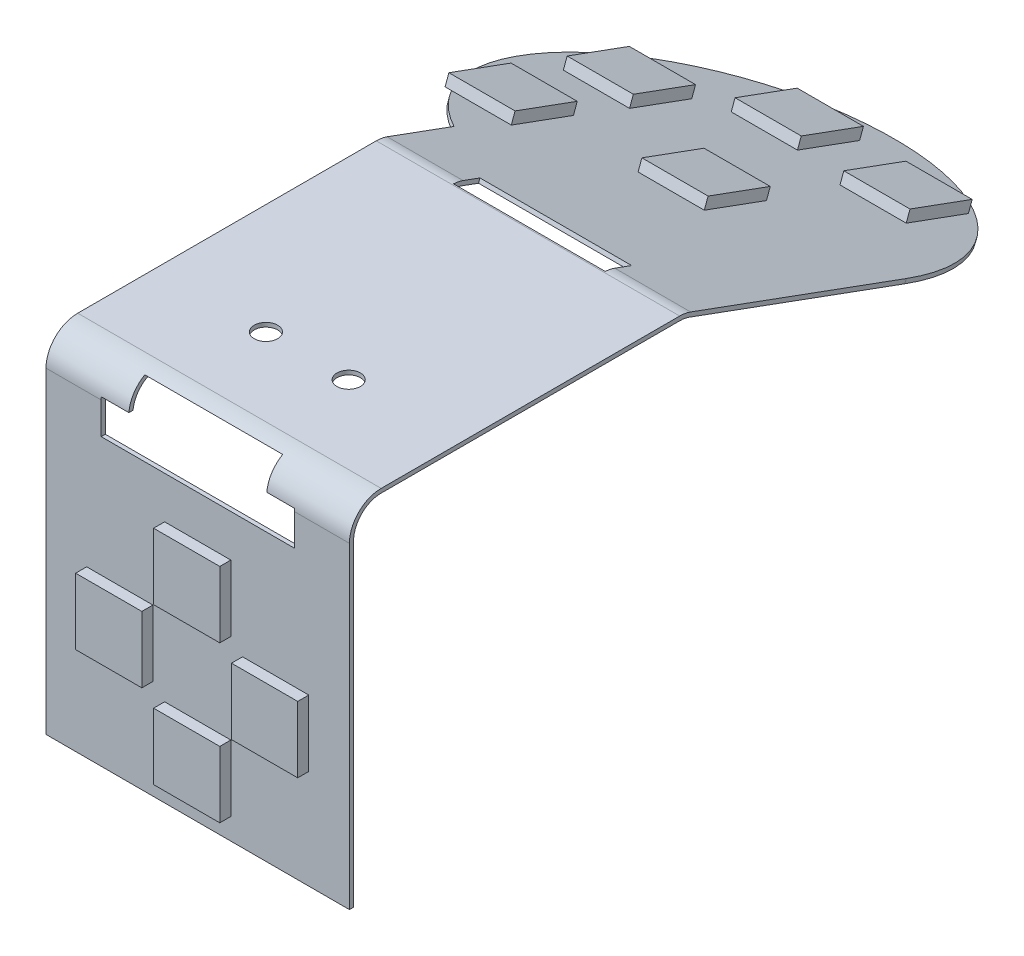
SolidWorks part; units mm, degrees
ref_plane "前视基准面" through (0, 0, 0) normal (0, 0, 1) x (1, 0, 0)
ref_plane "上视基准面" through (0, 0, 0) normal (0, 1, 0) x (1, 0, 0)
ref_plane "右视基准面" through (0, 0, 0) normal (1, 0, 0) x (0, 0, -1)
other "Configuration Table"
sketch "草图1" plane through (0, 0, 0) normal (1, 0, 0) x (0, 0, -1)
  line L0 (0, -25) -> (0, -2)
  line L1 (2, 0) -> (23.6457, 0)
  line L2 (24.3327, -0.1217) -> (52.1746, -10.3049)
  line L3 (-0.3, -25) -> (-0.3, -2)
  line L4 (2, 0.3) -> (23.6457, 0.3)
  line L5 (24.4358, 0.1601) -> (52.2777, -10.0231)
  line L6 (0, -25) -> (-0.3, -25)
  line L7 (52.2777, -10.0231) -> (52.1746, -10.3049)
  arc A0 (23.6457, 0) -> (24.3327, -0.1217) centre (23.6457, -2) cw
  arc A1 (0, -2) -> (2, 0) centre (2, -2) cw
  arc A2 (-0.3, -2) -> (2, 0.3) centre (2, -2) cw
  arc A3 (23.6457, 0.3) -> (24.4358, 0.1601) centre (23.6457, -2) cw
  point P7 (24, 0)
  point P10 (0, 0)
  dimension "D5" = 2
  dimension "D1" = 25
  dimension "D2" = 24
  dimension "D3" = 159.91
  dimension "D4" = 30
  dimension "D6" = 0.3
extrude "凸台-拉伸1" add sketch "草图1" along normal blind 22
sketch "草图2" plane through (0, 0, 0.3) normal (0, 0, 1) x (1, 0, 0)
  line L0 (22, 0.3) -> (0, 0.3) construction
  line L1 (4, -4.3) -> (18, -4.3)
  line L2 (4, -4.3) -> (4, -1.8)
  line L3 (4, -1.8) -> (18, -1.8)
  line L4 (18, -4.3) -> (18, -1.8)
  line L5 (6, -1.8) -> (16, -1.8)
  line L6 (6, -1.8) -> (6, 0)
  line L7 (6, 0) -> (16, 0)
  line L8 (16, -1.8) -> (16, 0)
  line L10 (11, -26.5654) -> (11, 3.7124) construction
  line L12 (0, -2) -> (0, -25) construction
  line L13 (22, -2) -> (22, -25) construction
  line M13 (22, -2) -> (0, -2)
  dimension "D1" = 1.8
  dimension "D2" = 2.5
  dimension "D3" = 0.3
  dimension "D4" = 14
  dimension "D5" = 10
extrude "切除-拉伸1" cut sketch "草图2" against normal blind 4 contours L3 L10 L7 L6 | L10 L5 L8 L7 | L1 L10 L2 M13 | L10 L1 L4 M13 | L10 L3 L2 M13 | L10 L4 L3 L5 M13 region at (7.5, -3.15, 0.3) region at (14.5, -3.15, 0.3) region at (7.5, -1.9, 0.3) region at (14.5, -1.9, 0.3) region at (13.5, -0.9, 0.3) region at (8.5, -0.9, 0.3)
sketch "草图3" plane through (0, 8.024, -2.9348) normal (0, 0.9392, -0.3435) x (1, 0, 0)
  line L0 (22, 52.5397) -> (22, 22.894) construction
  line L1 (22, 52.5397) -> (0, 52.5397) construction
  circle A0 centre (8, 39.5397) radius 14
  point P2 (6.1666, 43.208)
  point P5 (9.278, 41.7079)
  point P6 (7.5557, 40.2633)
  point P7 (0, 0)
  point P8 (7.5557, 39.8188)
  line M2 (0, 52.5397) -> (0, 22.894)
  line M4 (22, 22.894) -> (22, 52.5397)
  line M5 (22, 52.5397) -> (0, 52.5397)
  dimension "D1" = 28
  dimension "D2" = 13
extrude "切除-拉伸2" cut sketch "草图3" against normal through all contours A0 M4 M5 | A0 M5 M2 region at (19.6053, -8.9881, -49.4478) region at (0.8895, -9.8577, -51.8254)
extrude "凸台-拉伸2" add sketch "草图3<3>" against normal blind 0.3
sketch "草图3<3>" plane through (0, 8.024, -2.9348) normal (0, 0.9392, -0.3435) x (1, 0, 0) same geometry as "草图3"
sketch "草图4" plane through (0, 0, 0.3) normal (0, 0, 1) x (1, 0, 0)
  line L0 (-5.9466, -15.4) -> (23.7502, -15.4) construction
  line L1 (8.6, -7.35) -> (13.4, -7.35)
  line L2 (8.6, -7.35) -> (8.6, -12.15)
  line L3 (8.6, -12.15) -> (13.4, -12.15)
  line L4 (13.4, -7.35) -> (13.4, -12.15)
  line L5 (11, -28.2671) -> (11, 2.5503) construction
  line L6 (0, -2) -> (0, -25) construction
  line L7 (22, -2) -> (22, -25) construction
  line L8 (22, -25) -> (0, -25) construction
  line L9 (8.6, -18.65) -> (13.4, -18.65)
  line L10 (8.6, -18.65) -> (8.6, -23.45)
  line L11 (8.6, -23.45) -> (13.4, -23.45)
  line L12 (13.4, -18.65) -> (13.4, -23.45)
  line L14 (2.95, -13) -> (7.75, -13)
  line L15 (2.95, -13) -> (2.95, -17.8)
  line L16 (2.95, -17.8) -> (7.75, -17.8)
  line L17 (7.75, -13) -> (7.75, -17.8)
  line L18 (14.25, -13) -> (19.05, -13)
  line L19 (14.25, -13) -> (14.25, -17.8)
  line L20 (14.25, -17.8) -> (19.05, -17.8)
  line L21 (19.05, -13) -> (19.05, -17.8)
  dimension "D1" = 4.8
  dimension "D2" = 9.6
  dimension "D3" = 6.5
  dimension "D4" = 6.5
extrude "凸台-拉伸3" add sketch "草图4" along normal blind 0.8
sketch "草图5" plane through (0, 0.3, 0) normal (0, 1, 0) x (1, 0, 0)
  line L0 (11, -6.2283) -> (11, 16.6274) construction
  line L3 (0, 23.6457) -> (0, 2) construction
  line L4 (22, 23.6457) -> (22, 2) construction
  line L5 (22, 23.6457) -> (0, 23.6457) construction
  circle A0 centre (8, 7.6457) radius 0.85
  circle A1 centre (14, 7.6457) radius 0.85
  point P12 (14.286, 6.5162)
  point P13 (14.0837, 6.7475)
  point P14 (13.9604, 6.7191)
  point P15 (13.9984, 6.7286)
  point P18 (0, 0)
  point P20 (12.1537, 6.6694)
  dimension "D1" = 1.7
  dimension "D2" = 16
  dimension "D3" = 3
extrude "切除-拉伸3" cut sketch "草图5" against normal through all
sketch "草图6" plane through (0, 8.024, -2.9348) normal (0, 0.9392, -0.3435) x (1, 0, 0)
  line L0 (11, 16.3664) -> (11, 30.7303) construction
  line L1 (5.5, 22.2) -> (16.5, 22.2)
  line L2 (5.5, 22.2) -> (5.5, 24.2)
  line L3 (5.5, 24.2) -> (16.5, 24.2)
  line L4 (16.5, 22.2) -> (16.5, 24.2)
  line L7 (0, 22.1039) -> (0, 1.7753) construction
  line L8 (22, 22.1039) -> (22, 1.7753) construction
  dimension "D1" = 11
  dimension "D2" = 2
  dimension "D3" = 22.2
extrude "切除-拉伸4" cut sketch "草图6" against normal blind 1
sketch "草图7" plane through (0, 8.024, -2.9348) normal (0, 0.9392, -0.3435) x (1, 0, 0)
  line L1 (7.3385, 34.4514) -> (12.1385, 34.4514)
  line L2 (7.3385, 34.4514) -> (7.3385, 39.2514)
  line L3 (7.3385, 39.2514) -> (12.1385, 39.2514)
  line L4 (12.1385, 34.4514) -> (12.1385, 39.2514)
  line L5 (11.7188, 45.3744) -> (16.5188, 45.3744)
  line L6 (11.7188, 45.3744) -> (11.7188, 50.1744)
  line L7 (11.7188, 50.1744) -> (16.5188, 50.1744)
  line L8 (16.5188, 45.3744) -> (16.5188, 50.1744)
  line L9 (7.6196, 46.4557) -> (2.8196, 46.4557)
  line L10 (7.6196, 46.4557) -> (7.6196, 51.2557)
  line L11 (7.6196, 51.2557) -> (2.8196, 51.2557)
  line L12 (2.8196, 46.4557) -> (2.8196, 51.2557)
  line L13 (0.9105, 40.6376) -> (-3.8895, 40.6376)
  line L14 (0.9105, 40.6376) -> (0.9105, 45.4376)
  line L15 (0.9105, 45.4376) -> (-3.8895, 45.4376)
  line L16 (-3.8895, 40.6376) -> (-3.8895, 45.4376)
  line L17 (0.748, 31.6791) -> (-4.052, 31.6791)
  line L18 (0.748, 31.6791) -> (0.748, 36.4791)
  line L19 (0.748, 36.4791) -> (-4.052, 36.4791)
  line L20 (-4.052, 31.6791) -> (-4.052, 36.4791)
  dimension "D1" = 4.8
extrude "凸台-拉伸4" add sketch "草图7" along normal blind 0.8
